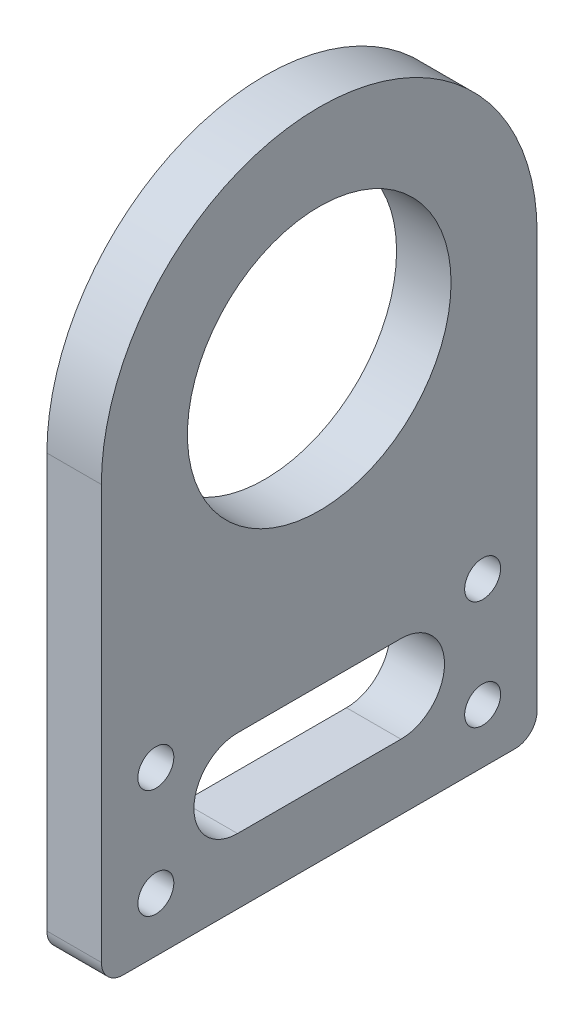
SolidWorks part; units mm, degrees
material "5052-H34"
ref_plane "正面" through (0, 0, 0) normal (0, 0, 1) x (1, 0, 0)
ref_plane "平面" through (0, 0, 0) normal (0, 1, 0) x (1, 0, 0)
ref_plane "右側面" through (0, 0, 0) normal (1, 0, 0) x (0, 0, -1)
sketch "ｽｹｯﾁ1" plane through (0, 0, 0) normal (1, 0, 0) x (0, 0, -1)
  line L0 (-20, 0) -> (-20, -40)
  line L1 (-20, -40) -> (20, -40)
  line L2 (20, -40) -> (20, 0)
  line L3 (0, 0) -> (0, -30) construction
  line L4 (-7.5, -30) -> (7.5, -30) construction
  line L5 (-15, -25) -> (15, -25) construction
  line L6 (-15, -25) -> (-15, -35) construction
  line L7 (-15, -35) -> (15, -35) construction
  line L8 (15, -25) -> (15, -35) construction
  line L9 (-15, -25) -> (15, -35) construction
  line L10 (-15, -35) -> (15, -25) construction
  line L11 (-7.5, -26) -> (7.5, -26)
  line L12 (-7.5, -34) -> (7.5, -34)
  circle A0 centre (0, 0) radius 12.1
  arc A1 (20, 0) -> (-20, 0) centre (0, 0) ccw
  circle A2 centre (15, -25) radius 1.65
  circle A3 centre (15, -35) radius 1.65
  circle A4 centre (-15, -25) radius 1.65
  circle A5 centre (-15, -35) radius 1.65
  arc A6 (-7.5, -26) -> (-7.5, -34) centre (-7.5, -30) ccw
  arc A7 (7.5, -34) -> (7.5, -26) centre (7.5, -30) ccw
  point P19 (0, -30)
  dimension "D1" = 24.2
  dimension "D2" = 40
  dimension "D7" = 3.3
  dimension "D3" = 40
  dimension "D4" = 10
  dimension "D5" = 10
  dimension "D6" = 30
  dimension "D8" = 8
  dimension "D9" = 15
extrude "ﾎﾞｽ - 押し出し1" add sketch "ｽｹｯﾁ1" along normal blind 5
fillet "ﾌｨﾚｯﾄ1" radius 2 2 edges at (2.5, -40, -20) (2.5, -40, 20)
